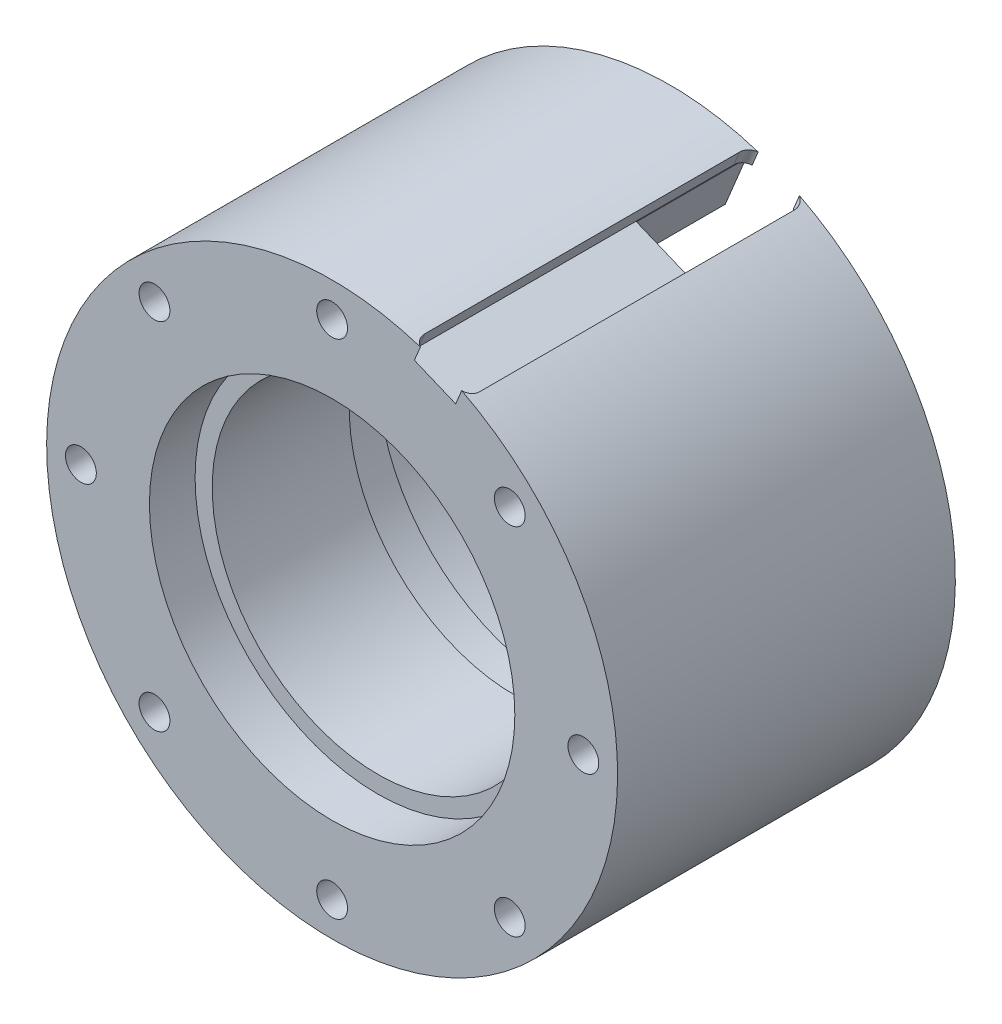
SolidWorks part; units mm, degrees
ref_plane "Front Plane" through (0, 0, 0) normal (0, 0, 1) x (1, 0, 0)
ref_plane "Top Plane" through (0, 0, 0) normal (0, 1, 0) x (1, 0, 0)
ref_plane "Right Plane" through (0, 0, 0) normal (1, 0, 0) x (0, 0, -1)
ref_axis "Z" through (0, 0, 11.479) along (0, 0, -1)
sketch "Sketch7" plane through (0, 0, 0) normal (0, 1, 0) x (1, 0, 0)
  line L0 (16, 10) -> (16, 6)
  line L2 (16, 6) -> (14.5, 6)
  line L3 (16, 10) -> (19, 10)
  line L4 (19, 10) -> (19, 19.58)
  line L5 (19, 19.58) -> (25, 19.58)
  line L6 (25, 19.58) -> (25, -10)
  line L7 (24.7452, 0) -> (-6.4078, 0) construction
  line L8 (16, -6) -> (14.5, -6)
  line L9 (16, -10) -> (16, -6)
  line L10 (14.5, 6) -> (14.5, -6)
  line L11 (25, -10) -> (16, -10)
  line L12 (0, -11.479) -> (0, 21.059) construction
  dimension "D2" = 4
  dimension "D4" = 6
  dimension "D6" = 6
  dimension "D7" = 9.58
  dimension "D1" = 14.5
  dimension "D3" = 16
  dimension "D5" = 25
revolve "Revolve1" add sketch "Sketch7" angle 360 about axis through (0, 0, 11.479) along (0, 0, -1)
sketch "Sketch3" plane through (0, 0, 0) normal (0, 0, 1) x (1, 0, 0)
  line L1 (0, 25) -> (0, 19) construction
  circle A0 centre (0, 22) radius 1.35
  circle A1 centre (0, 0) radius 25 construction
  circle A6 centre (0, 0) radius 19 construction
  dimension "D1" = 2.7
extrude "Cut-Extrude2" cut sketch "Sketch3" against normal through all both and the other way through all
sketch "Sketch4" plane through (0, 0, -10) normal (0, 0, -1) x (-1, 0, 0)
  circle A0 centre (0, 22) radius 2.25
  circle A1 centre (0, 22) radius 1.35 construction
  dimension "D1" = 4.5
extrude "Cut-Extrude4" cut sketch "Sketch4" against normal blind 2.5 and the other way through all
chamfer "Chamfer1" distance 0.1 angle 45 1 edges at (-1.35, 22, -7.5)
pattern_circular "CirPattern3" count 4 over 360 about axis through (0, 0, 11.479) along (0, 0, -1) of "Cut-Extrude4"
pattern_circular "CirPattern2" count 8 over 360 about axis through (0, 0, 11.479) along (0, 0, -1) of "Cut-Extrude2"
ref_plane "Plane1" through (0, 0, -14.79) normal (0, 0, -1) x (-1, 0, 0)
ref_plane "Plane2" through (0, 0, 0) normal (0.9239, -0.3827, 0) x (0, 0, -1)
sketch "Sketch8" plane through (0, 0, 0) normal (0, 0, 1) x (1, 0, 0)
  line L0 (0, 0) -> (9.0122, 21.7574) construction
  line L1 (-3.4729, -8.3842) -> (3.4729, 8.3842) construction
  dimension "D1" = 23.55
ref_plane "Plane3" through (9.0122, 21.7574, 0) normal (-0.3827, -0.9239, 0) x (-0.9239, 0.3827, 0)
sketch "Sketch9" plane through (9.0122, 21.7574, 0) normal (-0.3827, -0.9239, 0) x (-0.9239, 0.3827, 0)
  line L0 (2.5, -9) -> (2.5, 18.58) construction
  line L1 (1.5, 19.58) -> (-1.5, 19.58) construction
  line L3 (-1.5, -10) -> (1.5, -10) construction
  line L4 (0, -10) -> (0, 19.58) construction
  line L5 (-2.5, -9) -> (-2.5, 18.58) construction
  line L7 (0, 9.075) -> (0, -9.075) construction
  line L9 (-2.6, -9) -> (-2.6, 18.58)
  line L10 (1.5, 19.68) -> (-1.5, 19.68)
  line L11 (2.6, -9) -> (2.6, 18.58)
  line L12 (-1.5, -10.1) -> (1.5, -10.1)
  arc A0 (2.5, 18.58) -> (1.5, 19.58) centre (1.5, 18.58) ccw construction
  arc A3 (1.5, -10) -> (2.5, -9) centre (1.5, -9) ccw construction
  arc A4 (-1.5, -10) -> (-2.5, -9) centre (-1.5, -9) cw construction
  arc A5 (-2.5, 18.58) -> (-1.5, 19.58) centre (-1.5, 18.58) cw construction
  arc A6 (-2.6, 18.58) -> (-1.5, 19.68) centre (-1.5, 18.58) cw
  arc A7 (2.6, 18.58) -> (1.5, 19.68) centre (1.5, 18.58) ccw
  arc A8 (1.5, -10.1) -> (2.6, -9) centre (1.5, -9) ccw
  arc A9 (-1.5, -10.1) -> (-2.6, -9) centre (-1.5, -9) cw
  dimension "D3" = 1
  dimension "D1" = 29.58
  dimension "D2" = 5
  dimension "D4" = 10
extrude "Cut-Extrude5" cut sketch "Sketch9" against normal through all
sketch "Sketch10" plane through (0, 0, 0) normal (0.9239, -0.3827, 0) x (0, 0, -1)
  line L0 (0, 0) -> (10, 0) construction
  line L1 (10, 23.55) -> (10, 0) construction
  line L3 (10, 23.55) -> (19.58, 23.55)
  line L4 (10, 23.55) -> (10, 17.55)
  line L5 (10, 17.55) -> (19.58, 17.55)
  line L6 (19.58, 23.55) -> (19.58, 17.55)
  dimension "D1" = 10
  dimension "D2" = 9.58
  dimension "D3" = 6
  dimension "D4" = 23.55
extrude "Cut-Extrude6" cut sketch "Sketch10" against normal blind 2.55 and the other way blind 2.55
equation "\"BearingBaseDistance\"= 12"
equation "\"BearingOD\"= 32"
equation "\"BearingHeight\"= 4"
equation "\"SeatsOD\"= \"BearingOD\" + 10"
equation "\"WireHarnessHeight\"= 0.05in * 4 + 4.5"
equation "\"OuterWallWidth\"= 6"
equation "\"OverallOD\" = 50"
equation "\"BearingID\" = 25"
equation "\"OverallHeight\"= \"WireHarnessHeight\" + \"BearingHeight\"*2 + \"BearingBaseDistance\""
equation "\"RetainingRingThickness\" = 1.30"
equation "\"RetaininRingGrooveDiameter\" = 23.9"
equation "\"ShaftLengthAfterFlange\" = 2*\"BearingHeight\" + \"BearingBaseDistance\" + \"RetainingRingThickness\"*2\t'give a retaining ring thickness of extra clearance"
equation "\"RetainingRingGrooveBase\" = \"ShaftLengthAfterFlange\" - \"RetainingRingThickness\"*2"
equation "\"CoverThickness\" = 1"
equation "\"CoverClearance\" = 1"
equation "\"FlangHeight\" = \"CoverThickness\" + \"CoverClearance\" + \"WireHarnessHeight\""
equation "\"OuterHousingHeight\" = \"WireHarnessHeight\" + \"BearingHeight\"*2 + \"BearingBaseDistance\""
equation "\"PCBWidth\" = 5"
equation "\"PCBHeight\" = \"OuterHousingHeight\" "
equation "\"PCBThickness\" = 1"
equation "\"NormalDistSidewallPCBToZ\" = 23.55\t'radial distance from the z axis to pcb origin on the top/connector side"
equation "\"PCBSidewallCutoutClearance\" = 0.1"
equation "\"D3@Sketch7\"=\"BearingOD\"/2"
equation "\"D4@Sketch7\"=\"BearingBaseDistance\"/2"
equation "\"D7@Sketch7\"=\"WireHarnessHeight\""
equation "\"D6@Sketch7\"=\"OuterWallWidth\""
equation "\"D5@Sketch7\"=\"OverallOD\"/2"
equation "\"D1@Sketch8\"=\"NormalDistSidewallPCBToZ\""
equation "\"D1@Sketch9\"=\"PCBHeight\""
equation "\"D2@Sketch9\"=\"PCBWidth\""
equation "\"D4@Sketch9\"=\"BearingHeight\"+\"BearingBaseDistance\"/2"
equation "\"D5@Sketch9\"=\"PCBSidewallCutoutClearance\""
equation "\"D1@Sketch10\"=\"BearingHeight\"+\"BearingBaseDistance\"/2"
equation "\"D2@Sketch10\"=\"WireHarnessHeight\""
equation "\"D3@Sketch10\"=\"OuterWallWidth\""
equation "\"D4@Sketch10\"=\"NormalDistSidewallPCBToZ\""
